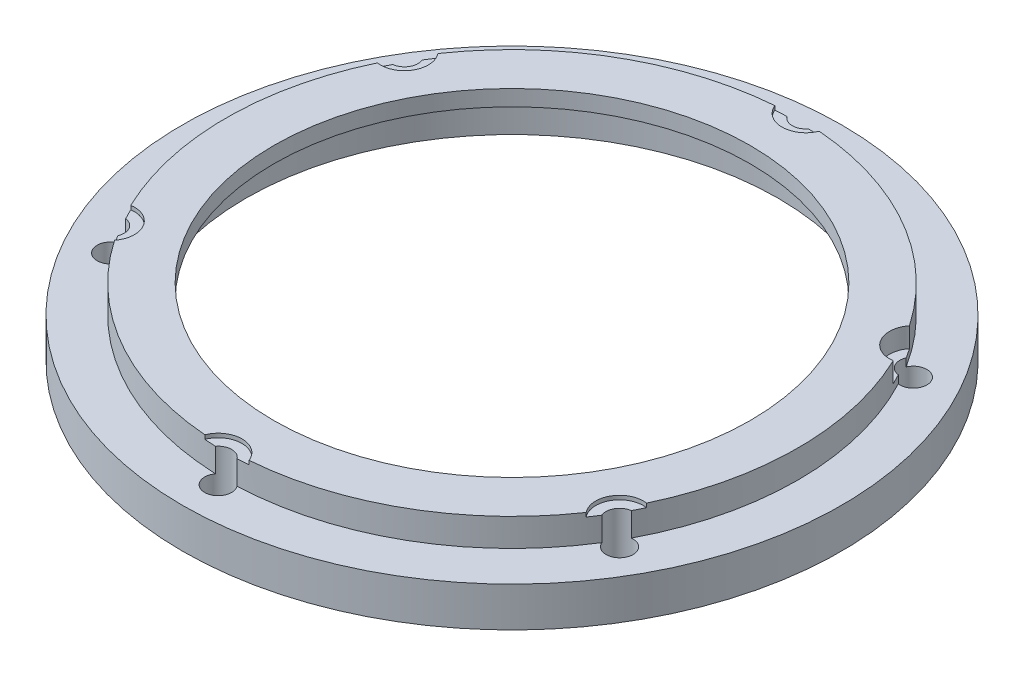
SolidWorks part; units mm, degrees
ref_plane "前视基准面" through (0, 0, 0) normal (0, 0, 1) x (1, 0, 0)
ref_plane "上视基准面" through (0, 0, 0) normal (0, 1, 0) x (1, 0, 0)
ref_plane "右视基准面" through (0, 0, 0) normal (1, 0, 0) x (0, 0, -1)
sketch "草图2" plane through (0, 0, 0) normal (1, 0, 0) x (0, 0, -1)
  line L9 (-30, 0) -> (-30, 2)
  line L10 (-30, 2) -> (-36, 2)
  line L11 (-30, 0) -> (-33.5, 0)
  line L12 (-33.5, 0) -> (-33.5, -5.5)
  line L13 (-33.5, -5.5) -> (-35, -5.5)
  line L14 (-35, -5.5) -> (-35, -6.5)
  line L15 (-35, -6.5) -> (-41.5, -6.5)
  line L16 (-36, 2) -> (-36, -1.5)
  line L17 (-36, -1.5) -> (-41.5, -1.5)
  line L18 (-41.5, -1.5) -> (-41.5, -6.5)
ref_axis "基准轴1" through (0, 0, 0) along (0, 1, 0)
revolve "旋转1" add sketch "草图2" angle 360 about axis through (0, 0, 0) along (0, 1, 0)
sketch "草图3" plane through (0, -1.5, 0) normal (0, 1, 0) x (1, 0, 0)
  circle A0 centre (0, 37) radius 1.7
  circle A1 centre (32.0429, 18.5) radius 1.7
  circle A2 centre (32.0429, -18.5) radius 1.7
  circle A3 centre (0, -37) radius 1.7
  circle A4 centre (-32.0429, -18.5) radius 1.7
  circle A5 centre (-32.0429, 18.5) radius 1.7
  point P16 (0, 0)
  dimension "D1" = 6
extrude "切除-拉伸1" cut sketch "草图3" against normal blind 10 and the other way up to next
sketch "草图4" plane through (0, -1.5, 0) normal (0, 1, 0) x (1, 0, 0)
  circle A0 centre (0, 37) radius 3
  circle A1 centre (32.0429, 18.5) radius 3
  circle A2 centre (32.0429, -18.5) radius 3
  circle A3 centre (0, -37) radius 3
  circle A4 centre (-32.0429, -18.5) radius 3
  circle A5 centre (-32.0429, 18.5) radius 3
  point P16 (0, 0)
  dimension "D1" = 6
extrude "切除-拉伸2" cut sketch "草图4" along normal blind 3 from offset 3
sketch "草图7" plane through (0, -1.5, 0) normal (0, 1, 0) x (1, 0, 0)
  circle A0 centre (32.0429, 18.5) radius 3
extrude "切除-拉伸3" cut sketch "草图7" along normal blind 10
sketch "草图8" plane through (0, -1.5, 0) normal (0, 1, 0) x (1, 0, 0)
  arc A1 (29.6894, 20.3603) -> (32.4772, 15.5316) centre (0, 0) cw
  arc A2 (29.6894, 20.3603) -> (32.4772, 15.5316) centre (32.0429, 18.5) ccw
  arc A3 (32.4772, -15.5316) -> (32.4772, 15.5316) centre (0, 0) ccw construction
  point P12 (0, 0)
  circle M2 centre (32.0429, 18.5) radius 1.7
  arc M4 (29.6894, 20.3603) -> (32.4772, 15.5316) centre (32.0429, 18.5) ccw
extrude "凸台-拉伸1" add sketch "草图8" along normal blind 1 contours A1 M4 M2 region at (30.3467, -1.5, -17.5207)
